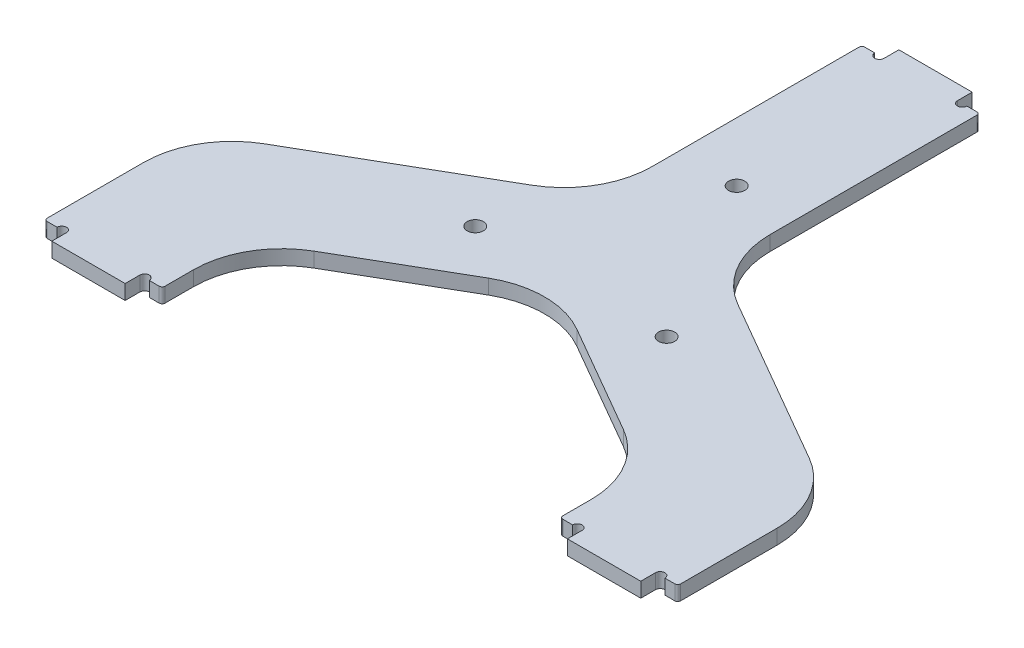
SolidWorks part; units mm, degrees
material "Hexcel AS4C (3000 丝)"
ref_plane "前视基准面" through (0, 0, 0) normal (0, 0, 1) x (1, 0, 0)
ref_plane "上视基准面" through (0, 0, 0) normal (0, 1, 0) x (1, 0, 0)
ref_plane "右视基准面" through (0, 0, 0) normal (1, 0, 0) x (0, 0, -1)
other "Configuration Table"
sketch "草图1" plane through (0, 0, 0) normal (0, 1, 0) x (1, 0, 0)
  line L0 (0, 66.645) -> (0, 0) construction
  line L1 (0, 0) -> (-61.257, -35.3667) construction
  line L2 (0, 0) -> (64.9836, -37.5183) construction
  line L3 (-20, 100) -> (20, 100)
  line L4 (20, 100) -> (20, 11.547)
  line L5 (20, 11.547) -> (87.5, -27.4241)
  line L7 (0, 0) -> (89.4221, 51.6279) construction
  line L8 (0, 0) -> (0, -63.446) construction
  line L9 (0, 0) -> (-78.7072, 45.4416) construction
  line L10 (0, -23.094) -> (67.5, -62.0652)
  line L11 (-20, 100) -> (-20, 11.547)
  line L12 (-20, 11.547) -> (-87.5, -27.4241)
  line L14 (0, -23.094) -> (-67.5, -62.0652)
  line L15 (-116.2493, -90) -> (125.7289, -90) construction
  line L16 (87.5, -27.4241) -> (107.5, -38.9711)
  line L17 (107.5, -38.9711) -> (107.5, -90)
  line L18 (67.5, -62.0652) -> (67.5, -90)
  line L19 (67.5, -90) -> (107.5, -90)
  line L20 (-67.5, -90) -> (-107.5, -90)
  line L21 (-67.5, -62.0652) -> (-67.5, -90)
  line L22 (-107.5, -38.9711) -> (-107.5, -90)
  line L23 (-87.5, -27.4241) -> (-107.5, -38.9711)
  point P15 (77.9423, -45)
  point P17 (0, 100)
  dimension "D1" = 190
  dimension "D2" = 120
  dimension "D3" = 60
  dimension "D4" = 60
  dimension "D5" = 100
  dimension "D6" = 135
  dimension "D7" = 20
  dimension "D8" = 40
extrude "凸台-拉伸1" add sketch "草图1" along normal blind 5
sketch "草图3" plane through (0, 5, 0) normal (0, 1, 0) x (1, 0, 0)
  line L0 (0, 0) -> (0, 55.4456) construction
  line L1 (0, 0) -> (-62.5545, -36.1159) construction
  line L2 (0, 0) -> (50.5729, -29.1983) construction
  line L3 (107.5, -38.9711) -> (20, 11.547) construction
  line L4 (0, -23.094) -> (67.5, -62.0652) construction
  line L5 (-20, 11.547) -> (-107.5, -38.9711) construction
  line L6 (-67.5, -62.0652) -> (0, -23.094) construction
  line L7 (-32.475, -18.7494) -> (32.475, -18.7494) construction
  circle A0 centre (0, 37.4989) radius 2.75
  circle A1 centre (32.475, -18.7494) radius 2.75
  circle A2 centre (-32.475, -18.7494) radius 2.75
  circle A3 centre (0, 0) radius 37.4989 construction
  dimension "D1" = 5.5
  dimension "D2" = 64.95
extrude "切除-拉伸1" cut sketch "草图3" against normal blind 5 contours A0 | A1 | A2
sketch "草图4" plane through (0, 5, 0) normal (0, 1, 0) x (1, 0, 0)
  line L0 (0, 0) -> (0, 135.8563) construction
  line L1 (20, 100) -> (-20, 100) construction
  line L2 (-12.5, 100) -> (12.5, 100)
  line L3 (-12.5, 100) -> (-12.5, 105)
  line L4 (-12.5, 105) -> (12.5, 105)
  line L5 (12.5, 100) -> (12.5, 105)
  line L6 (87.5, -13.6383) -> (87.5, -101.0311) construction
  line L7 (67.5, -62.0652) -> (67.5, -90) construction
  line L8 (107.5, -90) -> (107.5, -38.9711) construction
  line L9 (67.5, -90) -> (107.5, -90) construction
  line L10 (75, -90) -> (100, -90)
  line L11 (75, -90) -> (75, -95)
  line L12 (75, -95) -> (100, -95)
  line L13 (100, -90) -> (100, -95)
  line L14 (-75, -95) -> (-100, -95)
  line L15 (-100, -90) -> (-100, -95)
  line L16 (-75, -90) -> (-100, -90)
  line L17 (-75, -90) -> (-75, -95)
  line M22 (-107.5, -90) -> (-67.5, -90)
  line M25 (67.5, -90) -> (107.5, -90)
  dimension "D3" = 5
  dimension "D1" = 5
  dimension "D2" = 25
  dimension "D4" = 25
extrude "凸台-拉伸2" add sketch "草图4" against normal blind 5 contours L17 L15 L14 M22 | L13 L11 L12 M25 | L4 L5 L2 L3 region at (87.5, 5, 92.5) region at (-87.5, 5, 92.5)
sketch "草图5" plane through (0, 5, 0) normal (0, 1, 0) x (1, 0, 0)
  line L0 (20, 100) -> (12.5, 100) construction
  line L1 (-12.5, 100) -> (-12.5, 105) construction
  line L2 (12.5, 100) -> (12.5, 105) construction
  line L3 (-12.5, 100) -> (-20, 100) construction
  line L4 (-75, -90) -> (-67.5, -90) construction
  line L5 (-107.5, -90) -> (-100, -90) construction
  line L6 (100, -90) -> (107.5, -90) construction
  line L7 (67.5, -90) -> (75, -90) construction
  line L8 (-75, -90) -> (-75, -95) construction
  line L9 (-100, -90) -> (-100, -95) construction
  line L10 (75, -90) -> (75, -95) construction
  line L11 (100, -90) -> (100, -95) construction
  circle A0 centre (14.05, 100) radius 1.55
  circle A1 centre (-14.05, 100) radius 1.55
  circle A2 centre (-73.45, -90) radius 1.55
  circle A3 centre (-101.55, -90) radius 1.55
  circle A4 centre (101.55, -90) radius 1.55
  circle A5 centre (73.45, -90) radius 1.55
  dimension "D2" = 3.1
extrude "切除-拉伸2" cut sketch "草图5" against normal blind 5
fillet "圆角1" radius 30 7 edges at (-107.5, 2.5, 38.9711) (-67.5, 2.5, 62.0652) (67.5, 2.5, 62.0652) (107.5, 2.5, 38.9711) (20, 2.5, -11.547) (0, 2.5, 23.094) (-20, 2.5, -11.547)
fillet "圆角2" radius 1 6 edges at (-67.5, 2.5, 90) (-107.5, 2.5, 90) (67.5, 2.5, 90) (107.5, 2.5, 90) (-20, 2.5, -100) (20, 2.5, -100)
other "移动面1" flip direction yes face at (14.05, 2.5, -99.225) face at (12.5, 2.5, -102.5) face at (-14.05, 2.5, -99.225) face at (-12.5, 2.5, -102.5) face at (-100, 2.5, 92.5) face at (-101.55, 2.5, 89.225) face at (-75, 2.5, 92.5) face at (-73.45, 2.5, 89.225) face at (100, 2.5, 92.5) face at (101.55, 2.5, 89.225) face at (75, 2.5, 92.5) face at (73.45, 2.5, 89.225) offset 0.05 parameters "D1"=0.05
